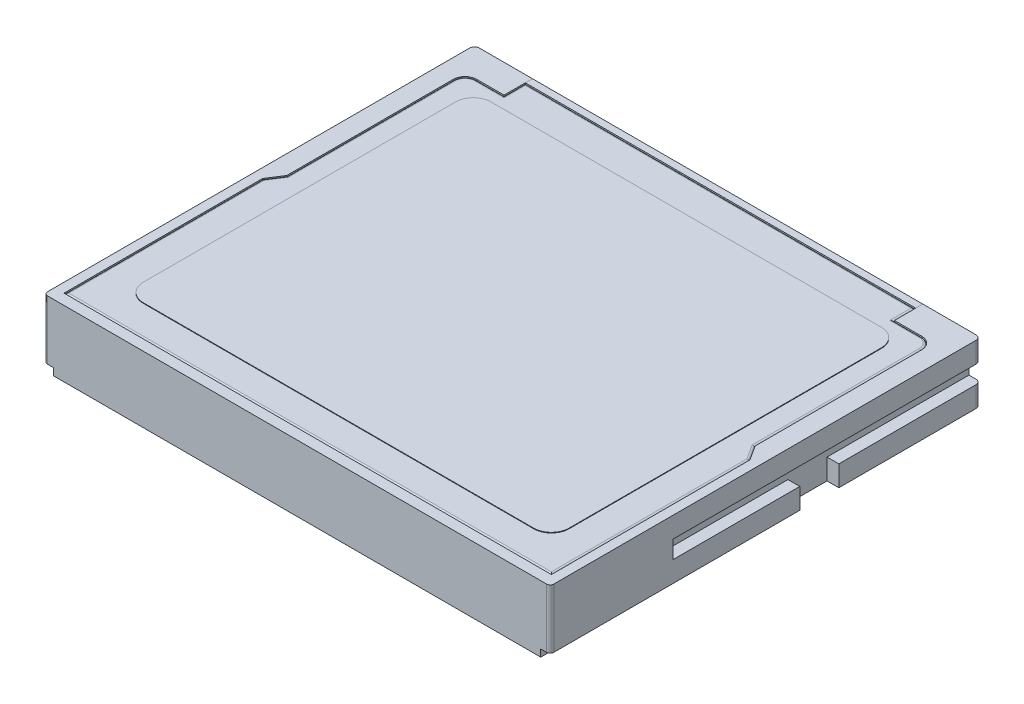
SolidWorks part; units mm, degrees
material "Duranickel(R) 301"
ref_plane "Alzado" through (0, 0, 0) normal (0, 0, 1) x (1, 0, 0)
ref_plane "Planta" through (0, 0, 0) normal (0, 1, 0) x (1, 0, 0)
ref_plane "Vista lateral" through (0, 0, 0) normal (1, 0, 0) x (0, 0, -1)
sketch "Croquis1" plane through (0, 0, 0) normal (0, 0, 1) x (1, 0, 0)
  line L1 (-21.4, 2.5) -> (21.4, 2.5)
  line L2 (-21.4, 2.5) -> (-21.4, -2.5)
  line L3 (-21.4, -2.5) -> (21.4, -2.5)
  line L4 (21.4, 2.5) -> (21.4, -2.5)
  dimension "D1" = 5
  dimension "D2" = 2.5
  dimension "D3" = 42.8
  dimension "D4" = 21.4
extrude "Extruir1" add sketch "Croquis1" along normal blind 36.4
sketch "Croquis2" plane through (0, 0, 0) normal (0, 0, -1) x (-1, 0, 0)
  line L1 (21.946, 0.75) -> (20.4, 0.75)
  line L2 (21.946, 0.75) -> (21.946, -0.75)
  line L3 (21.946, -0.75) -> (20.4, -0.75)
  line L4 (20.4, 0.75) -> (20.4, -0.75)
  line L6 (21.4, 2.5) -> (21.4, -2.5) construction
  line L7 (0, 0) -> (0, -7.9617) construction
  line L8 (-20.4, 0.75) -> (-20.4, -0.75)
  line L9 (-21.946, -0.75) -> (-20.4, -0.75)
  line L10 (-21.946, 0.75) -> (-21.946, -0.75)
  line L11 (-21.946, 0.75) -> (-20.4, 0.75)
  point P8 (21.4, 0)
  dimension "D1" = 1.5
  dimension "D2" = 0.75
  dimension "D3" = 1
extrude "Cortar-Extruir1" cut sketch "Croquis2" against normal blind 26
sketch "Croquis3" plane through (0, -2.5, 0) normal (0, -1, 0) x (1, 0, 0)
  line L0 (-21.4, 0) -> (21.4, 0) construction
  line L1 (20.4, 12) -> (23.6007, 12)
  line L2 (20.4, 12) -> (20.4, 15.3)
  line L3 (20.4, 15.3) -> (23.6007, 15.3)
  line L4 (23.6007, 12) -> (23.6007, 15.3)
  line L5 (20.4, 26) -> (20.4, 0) construction
  line L6 (0, 0) -> (0, -7.9498) construction
  line L7 (-23.6007, 12) -> (-23.6007, 15.3)
  line L8 (-20.4, 15.3) -> (-23.6007, 15.3)
  line L9 (-20.4, 12) -> (-20.4, 15.3)
  line L10 (-20.4, 12) -> (-23.6007, 12)
  dimension "D1" = 12
  dimension "D2" = 3.3
extrude "Cortar-Extruir2" cut sketch "Croquis3" against normal blind 2
sketch "Croquis4" plane through (0, 0, 0) normal (0, 0, -1) x (-1, 0, 0)
  line L1 (-16.5, 4.3681) -> (16.5, 4.3681)
  line L2 (-16.5, 4.3681) -> (-16.5, -3.9453)
  line L3 (-16.5, -3.9453) -> (16.5, -3.9453)
  line L4 (16.5, 4.3681) -> (16.5, -3.9453)
  dimension "D1" = 33
  dimension "D2" = 16.5
split line "Línea de partición1"
sketch "Croquis6" plane through (0, 0, 0) normal (0, 0, -1) x (-1, 0, 0)
  line L0 (0, -2.5) -> (0, -5.6564) construction
  line L1 (16.5, -2.5) -> (-16.5, -2.5) construction
  circle A0 centre (0, -0.625) radius 0.25
  circle A1 centre (0, 0.625) radius 0.25
  circle A2 centre (-1.25, -0.625) radius 0.25
  circle A3 centre (-1.25, 0.625) radius 0.25
  circle A4 centre (-2.5, -0.625) radius 0.25
  circle A5 centre (-2.5, 0.625) radius 0.25
  circle A6 centre (-3.75, -0.625) radius 0.25
  circle A7 centre (-3.75, 0.625) radius 0.25
  circle A8 centre (-5, -0.625) radius 0.25
  circle A9 centre (-5, 0.625) radius 0.25
  circle A10 centre (-6.25, -0.625) radius 0.25
  circle A11 centre (-6.25, 0.625) radius 0.25
  circle A12 centre (-7.5, -0.625) radius 0.25
  circle A13 centre (-7.5, 0.625) radius 0.25
  circle A14 centre (-8.75, -0.625) radius 0.25
  circle A15 centre (-8.75, 0.625) radius 0.25
  circle A16 centre (-10, -0.625) radius 0.25
  circle A17 centre (-10, 0.625) radius 0.25
  circle A18 centre (-11.25, -0.625) radius 0.25
  circle A19 centre (-11.25, 0.625) radius 0.25
  circle A20 centre (-12.5, -0.625) radius 0.25
  circle A21 centre (-12.5, 0.625) radius 0.25
  circle A22 centre (-13.75, -0.625) radius 0.25
  circle A23 centre (-13.75, 0.625) radius 0.25
  circle A24 centre (-15, -0.625) radius 0.25
  circle A25 centre (-15, 0.625) radius 0.25
  circle A26 centre (15, 0.625) radius 0.25
  circle A27 centre (15, -0.625) radius 0.25
  circle A28 centre (13.75, 0.625) radius 0.25
  circle A29 centre (13.75, -0.625) radius 0.25
  circle A30 centre (12.5, 0.625) radius 0.25
  circle A31 centre (12.5, -0.625) radius 0.25
  circle A32 centre (11.25, 0.625) radius 0.25
  circle A33 centre (11.25, -0.625) radius 0.25
  circle A34 centre (10, 0.625) radius 0.25
  circle A35 centre (10, -0.625) radius 0.25
  circle A36 centre (8.75, 0.625) radius 0.25
  circle A37 centre (8.75, -0.625) radius 0.25
  circle A38 centre (7.5, 0.625) radius 0.25
  circle A39 centre (7.5, -0.625) radius 0.25
  circle A40 centre (6.25, 0.625) radius 0.25
  circle A41 centre (6.25, -0.625) radius 0.25
  circle A42 centre (5, 0.625) radius 0.25
  circle A43 centre (5, -0.625) radius 0.25
  circle A44 centre (3.75, 0.625) radius 0.25
  circle A45 centre (3.75, -0.625) radius 0.25
  circle A46 centre (2.5, 0.625) radius 0.25
  circle A47 centre (2.5, -0.625) radius 0.25
  circle A48 centre (1.25, 0.625) radius 0.25
  circle A49 centre (1.25, -0.625) radius 0.25
  dimension "D1" = 0.5
  dimension "D2" = 0.625
extrude "Cortar-Extruir3" cut sketch "Croquis6" against normal blind 10
fillet "Redondeo1" radius 0.4 4 edges at (21.4, -1.625, 0) (21.4, 1.625, 0) (-21.4, -1.625, 0) (-21.4, 1.625, 0)
fillet "Redondeo2" radius 0.3 2 edges at (21.4, 0, 36.4) (-21.4, 0, 36.4)
chamfer "Chaflán1" distance 0.25 angle 45 50 edges at (-14.75, -0.625, 0) (-14.75, 0.625, 0) (-13.5, -0.625, 0) (-13.5, 0.625, 0) (-12.25, -0.625, 0) (-12.25, 0.625, 0) (-11, -0.625, 0) (-11, 0.625, 0) (-9.75, -0.625, 0) (-9.75, 0.625, 0) (-8.5, -0.625, 0) (-8.5, 0.625, 0) (-7.25, -0.625, 0) (-7.25, 0.625, 0) (-6, -0.625, 0) (-6, 0.625, 0) (-4.75, -0.625, 0) (-4.75, 0.625, 0) (-3.5, -0.625, 0) (-3.5, 0.625, 0) (-2.25, -0.625, 0) (-2.25, 0.625, 0) (-1, -0.625, 0) (-1, 0.625, 0) (-0.25, -0.625, 0) (-0.25, 0.625, 0) (1, -0.625, 0) (1, 0.625, 0) (2.25, -0.625, 0) (2.25, 0.625, 0) (3.5, 0.625, 0) (3.5, -0.625, 0) (4.75, -0.625, 0) (4.75, 0.625, 0) (6, -0.625, 0) (6, 0.625, 0) (7.25, -0.625, 0) (7.25, 0.625, 0) (8.5, 0.625, 0) (8.5, -0.625, 0) (9.75, -0.625, 0) (9.75, 0.625, 0) (11, -0.625, 0) (11, 0.625, 0) (12.25, 0.625, 0) (12.25, -0.625, 0) (13.5, -0.625, 0) (13.5, 0.625, 0) (14.75, -0.625, 0) (14.75, 0.625, 0)
sketch "Croquis7" plane through (0, -2.5, 0) normal (0, -1, 0) x (1, 0, 0)
  line L0 (-21.1, 36.4) -> (21.1, 36.4) construction
  line L1 (-20.6, 36.4) -> (20.6, 36.4)
  line L2 (-20.6, 36.4) -> (-20.6, 35.5)
  line L3 (-20.6, 35.5) -> (20.6, 35.5)
  line L4 (20.6, 36.4) -> (20.6, 35.5)
  dimension "D1" = 0.9
  dimension "D2" = 20.6
  dimension "D3" = 41.2
extrude "Extruir2" add sketch "Croquis7" along normal blind 0.6
sketch "Croquis8" plane through (0, -2.5, 0) normal (0, -1, 0) x (1, 0, 0)
  line L0 (-20.6, 35.5) -> (20.6, 35.5)
  line L1 (-20.6, 35.5) -> (20.6, 35.5) construction
  line L2 (20.6, 35.5) -> (20.6, 18.7165)
  line L3 (20.6, 18.7165) -> (19.8, 17.4725)
  line L4 (19.8, 17.4725) -> (19.8, 3.4)
  line L5 (18.8, 2.4) -> (16.5, 2.4)
  line L6 (16.5, 2.4) -> (16.5, 0.6)
  line L7 (16.5, 0.6) -> (-1.0335, 0.6)
  line L8 (21.4, 12) -> (21.4, 0.4) construction
  line L9 (16.5, 0) -> (21, 0) construction
  line L10 (0, 35.5) -> (0, 41.56) construction
  line L11 (-16.5, 0.6) -> (1.0335, 0.6)
  line L12 (-16.5, 2.4) -> (-16.5, 0.6)
  line L13 (-18.8, 2.4) -> (-16.5, 2.4)
  line L14 (-19.8, 17.4725) -> (-19.8, 3.4)
  line L15 (-20.6, 18.7165) -> (-19.8, 17.4725)
  line L16 (-20.6, 35.5) -> (-20.6, 18.7165)
  arc A0 (19.8, 3.4) -> (18.8, 2.4) centre (18.8, 3.4) cw
  arc A1 (-19.8, 3.4) -> (-18.8, 2.4) centre (-18.8, 3.4) ccw
  line M22 (20.6, 35.5) -> (-20.6, 35.5)
  dimension "D5" = 1
  dimension "D1" = 16.5
  dimension "D2" = 1.6
  dimension "D3" = 0.6
  dimension "D4" = 2.4
extrude "Cortar-Extruir4" cut sketch "Croquis8" against normal blind 0.5 contours L14 A1 L13 L12 L11 L7 L6 L5 A0 L4 L3 L2 L0 L16 L15 M22
mirror "Simetría1" about plane through (0, 0, 0) normal (0, 1, 0) of "Cortar-Extruir4"
sketch "Croquis9" plane through (0, -2, 0) normal (0, -1, 0) x (1, 0, 0)
  line L24 (-19.8, 17.4725) -> (-19.8, 3.4)
  line L25 (-18.8, 2.4) -> (-16.5, 2.4)
  line L26 (-16.5, 2.4) -> (-16.5, 0.6)
  line L27 (-16.5, 0.6) -> (16.5, 0.6)
  line L28 (16.5, 0.6) -> (16.5, 2.4)
  line L29 (16.5, 2.4) -> (18.8, 2.4)
  line L30 (19.8, 3.4) -> (19.8, 17.4725)
  line L31 (19.8, 17.4725) -> (20.6, 18.7165)
  line L32 (20.6, 18.7165) -> (20.6, 35.5)
  line L33 (20.6, 35.5) -> (-20.6, 35.5)
  line L34 (-20.6, 35.5) -> (-20.6, 18.7165)
  line L35 (-20.6, 18.7165) -> (-19.8, 17.4725)
  line L36 (-19.8, 17.4725) -> (-19.8, 3.4)
  line L37 (-18.8, 2.4) -> (-16.5, 2.4)
  line L38 (-16.5, 2.4) -> (-16.5, 0.6)
  line L39 (-16.5, 0.6) -> (16.5, 0.6)
  line L40 (16.5, 0.6) -> (16.5, 2.4)
  line L41 (16.5, 2.4) -> (18.8, 2.4)
  line L42 (19.8, 3.4) -> (19.8, 17.4725)
  line L43 (19.8, 17.4725) -> (20.6, 18.7165)
  line L44 (20.6, 18.7165) -> (20.6, 35.5)
  line L45 (20.6, 35.5) -> (-20.6, 35.5)
  line L46 (-20.6, 35.5) -> (-20.6, 18.7165)
  line L47 (-20.6, 18.7165) -> (-19.8, 17.4725)
  arc A4 (-19.8, 3.4) -> (-18.8, 2.4) centre (-18.8, 3.4) ccw
  arc A5 (18.8, 2.4) -> (19.8, 3.4) centre (18.8, 3.4) ccw
  arc A6 (-19.8, 3.4) -> (-18.8, 2.4) centre (-18.8, 3.4) ccw
  arc A7 (18.8, 2.4) -> (19.8, 3.4) centre (18.8, 3.4) ccw
  dimension "D1" = 0
extrude "Extruir3" add sketch "Croquis9" along normal blind 0.5 separate body
fillet "Redondeo3" radius 0.2 14 edges at (-20.6, -2.5, 27.1083) (0, -2.5, 35.5) (20.6, -2.5, 27.1083) (20.2, -2.5, 18.0945) (19.8, -2.5, 10.4362) (19.5071, -2.5, 2.6929) (17.65, -2.5, 2.4) (16.5, -2.5, 1.5) (0, -2.5, 0.6) (-16.5, -2.5, 1.5) (-17.65, -2.5, 2.4) (-19.5071, -2.5, 2.6929) (-19.8, -2.5, 10.4362) (-20.2, -2.5, 18.0945)
sketch "Croquis10" plane through (0, 2, 0) normal (0, 1, 0) x (-1, 0, 0)
  line L12 (19.8, 3.4) -> (19.8, 17.4725)
  line L13 (19.8, 17.4725) -> (20.6, 18.7165)
  line L14 (20.6, 18.7165) -> (20.6, 35.5)
  line L15 (20.6, 35.5) -> (-20.6, 35.5)
  line L16 (-20.6, 35.5) -> (-20.6, 18.7165)
  line L17 (-20.6, 18.7165) -> (-19.8, 17.4725)
  line L18 (-19.8, 17.4725) -> (-19.8, 3.4)
  line L19 (-18.8, 2.4) -> (-16.5, 2.4)
  line L20 (-16.5, 2.4) -> (-16.5, 0.6)
  line L21 (-16.5, 0.6) -> (16.5, 0.6)
  line L22 (16.5, 0.6) -> (16.5, 2.4)
  line L23 (16.5, 2.4) -> (18.8, 2.4)
  line L24 (19.8, 3.4) -> (19.8, 17.4725)
  line L25 (19.8, 17.4725) -> (20.6, 18.7165)
  line L26 (20.6, 18.7165) -> (20.6, 35.5)
  line L27 (20.6, 35.5) -> (-20.6, 35.5)
  line L28 (-20.6, 35.5) -> (-20.6, 18.7165)
  line L29 (-20.6, 18.7165) -> (-19.8, 17.4725)
  line L30 (-19.8, 17.4725) -> (-19.8, 3.4)
  line L31 (-18.8, 2.4) -> (-16.5, 2.4)
  line L32 (-16.5, 2.4) -> (-16.5, 0.6)
  line L33 (-16.5, 0.6) -> (16.5, 0.6)
  line L34 (16.5, 0.6) -> (16.5, 2.4)
  line L35 (16.5, 2.4) -> (18.8, 2.4)
  arc A2 (-19.8, 3.4) -> (-18.8, 2.4) centre (-18.8, 3.4) ccw
  arc A3 (18.8, 2.4) -> (19.8, 3.4) centre (18.8, 3.4) ccw
  arc A4 (-19.8, 3.4) -> (-18.8, 2.4) centre (-18.8, 3.4) ccw
  arc A5 (18.8, 2.4) -> (19.8, 3.4) centre (18.8, 3.4) ccw
  dimension "D1" = 0
extrude "Extruir4" add sketch "Croquis10" along normal blind 0.5 separate body
fillet "Redondeo4" radius 0.2 14 edges at (-17.65, 2.5, 2.4) (-16.5, 2.5, 1.5) (0, 2.5, 0.6) (16.5, 2.5, 1.5) (17.65, 2.5, 2.4) (19.5071, 2.5, 2.6929) (19.8, 2.5, 10.4362) (20.2, 2.5, 18.0945) (20.6, 2.5, 27.1083) (0, 2.5, 35.5) (-20.6, 2.5, 27.1083) (-20.2, 2.5, 18.0945) (-19.8, 2.5, 10.4362) (-19.5071, 2.5, 2.6929)
sketch "Croquis11" plane through (0, 2.5, 0) normal (0, 1, 0) x (-1, 0, 0)
  line L1 (-16.5, 7.9771) -> (16.5, 7.9771)
  line L2 (-16.5, 7.9771) -> (-16.5, -4.3763)
  line L3 (-16.5, -4.3763) -> (16.5, -4.3763)
  line L4 (16.5, 7.9771) -> (16.5, -4.3763)
split line "Línea de partición2"
sketch "Croquis12" plane through (0, -2.5, 0) normal (0, -1, 0) x (1, 0, 0)
  line L1 (-16.5, 4.0989) -> (16.5, 4.0989)
  line L2 (-16.5, 4.0989) -> (-16.5, -2.9767)
  line L3 (-16.5, -2.9767) -> (16.5, -2.9767)
  line L4 (16.5, 4.0989) -> (16.5, -2.9767)
split line "Línea de partición3"
sketch "Croquis13" plane through (0, 2.5, 0) normal (0, 1, 0) x (-1, 0, 0)
  line L0 (-16.5, 0) -> (16.5, 0) construction
  line L1 (-16.5, 32.9) -> (16.5, 32.9)
  line L2 (-18, 31.4) -> (-18, 5)
  line L3 (-16.5, 3.5) -> (16.5, 3.5)
  line L4 (18, 31.4) -> (18, 5)
  line L5 (-21.1, 36.4) -> (21.1, 36.4) construction
  arc A0 (-16.5, 32.9) -> (-18, 31.4) centre (-16.5, 31.4) ccw
  arc A1 (16.5, 32.9) -> (18, 31.4) centre (16.5, 31.4) cw
  arc A2 (-18, 5) -> (-16.5, 3.5) centre (-16.5, 5) ccw
  arc A3 (16.5, 3.5) -> (18, 5) centre (16.5, 5) ccw
  point P11 (-18, 32.9)
  point P14 (18, 32.9)
  dimension "D5" = 1.5
  dimension "D1" = 36
  dimension "D2" = 18
  dimension "D3" = 3.5
  dimension "D4" = 3.5
extrude "Extruir5" add sketch "Croquis13" along normal blind 0.05 separate body
mirror "Simetría2" about plane through (0, 0, 0) normal (0, 1, 0) of bodies 110
